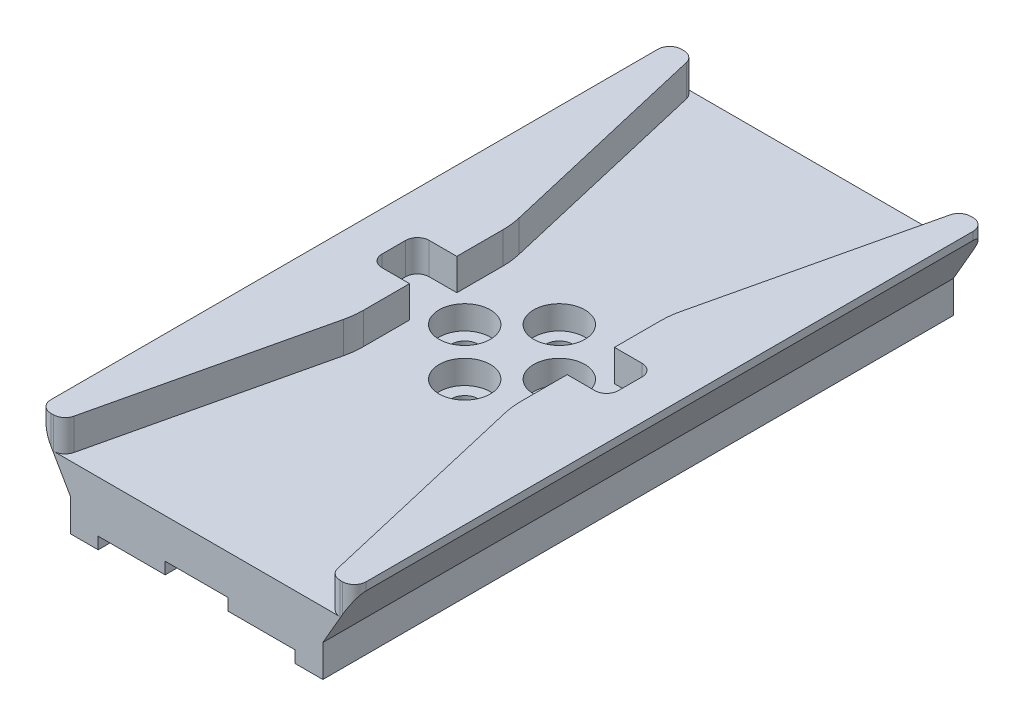
SolidWorks part; units mm, degrees
material "Сплав 2024"
ref_plane "Спереди" through (0, 0, 0) normal (0, 0, 1) x (1, 0, 0)
ref_plane "Сверху" through (0, 0, 0) normal (0, 1, 0) x (1, 0, 0)
ref_plane "Справа" through (0, 0, 0) normal (1, 0, 0) x (0, 0, -1)
sketch "Эскиз1" plane through (0, 0, 0) normal (0, 0, 1) x (1, 0, 0)
  line L0 (-20, 5) -> (-16, -1.9282)
  line L1 (-20, 6) -> (20, 6)
  line L2 (-25.6942, 6) -> (28.5829, 6) construction
  line L3 (-16, -6) -> (16, -6)
  line L4 (0, 6) -> (0, -6) construction
  line L5 (-22.304, 8.9907) -> (-15.6808, -2.4811) construction
  line L7 (-16, -1.9282) -> (-16, -6)
  line L9 (-20, 6) -> (-20, 5)
  line L10 (16, -1.9282) -> (16, -6)
  line L11 (20, 5) -> (16, -1.9282)
  line L12 (20, 6) -> (20, 5)
  point P15 (-20.5774, 6)
  dimension "D1" = 16
  dimension "D2" = 12
  dimension "D3" = 60
  dimension "D4" = 20.5774
  dimension "D6" = 20
  dimension "D7" = 1
extrude "Бобышка-Вытянуть1" add sketch "Эскиз1" along normal blind 80
sketch "Эскиз2" plane through (0, 6, 0) normal (0, 1, 0) x (1, 0, 0)
  line L0 (0, 0) -> (0, -80) construction
  line L1 (20, 0) -> (-20, 0) construction
  line L2 (20, -80) -> (-20, -80) construction
  line L3 (-17, 0) -> (-17, -80) construction
  line L4 (10, -50) -> (17, -80)
  line L5 (-17, 0) -> (-10, -30)
  line L6 (-10, -30) -> (-10, -50)
  line L7 (-10, -50) -> (-17, -80)
  line L8 (10, -30) -> (10, -50)
  line L9 (17, 0) -> (10, -30)
  line L10 (20, -40) -> (-20, -40) construction
  line L11 (-17, 0) -> (17, 0)
  line L12 (17, -80) -> (-17, -80)
  line L20 (-20, -80) -> (-20, 0) construction
  line L21 (20, -80) -> (20, 0) construction
  point P24 (-10, -40)
  dimension "D1" = 10
  dimension "D2" = 3
  dimension "D3" = 20
extrude "Вырез-Вытянуть1" cut sketch "Эскиз2" against normal blind 4
sketch "Эскиз3" plane through (0, 6, 0) normal (0, 1, 0) x (1, 0, 0)
  line L0 (20, -40) -> (-20, -40) construction
  line L4 (-10, -37) -> (-15, -37)
  line L5 (-10, -37) -> (-10, -43)
  line L6 (-10, -43) -> (-15, -43)
  line L7 (-15, -37) -> (-15, -43)
  line L8 (0, 0) -> (0, -80) construction
  line L9 (17, 0) -> (-17, 0) construction
  line L10 (-17, -80) -> (17, -80) construction
  line L11 (10, -37) -> (10, -43)
  line L12 (10, -43) -> (15, -43)
  line L13 (15, -37) -> (15, -43)
  line L14 (10, -37) -> (15, -37)
  line L15 (-10, -30) -> (-10, -50) construction
  line L16 (20, -80) -> (20, 0) construction
  line L17 (-20, -80) -> (-20, 0) construction
  point P12 (-10, -40)
  dimension "D1" = 6
  dimension "D2" = 5
extrude "Вырез-Вытянуть2" cut sketch "Эскиз3" against normal blind 4
fillet "Скругление1" radius 1.5 12 edges at (20, 5.5, 0) (20, 5.5, 80) (-20, 5.5, 80) (-20, 5.5, 0) (-15, 4, 43) (-15, 4, 37) (17, 4, 80) (-17, 4, 80) (17, 4, 0) (-17, 4, 0) (15, 4, 43) (15, 4, 37)
fillet "Скругление2" radius 10 4 edges at (10, 4, 50) (10, 4, 30) (-10, 4, 30) (-10, 4, 50)
sketch "Эскиз4" plane through (0, 2, 0) normal (0, 1, 0) x (1, 0, 0)
  line L0 (0, 0) -> (0, -80) construction
  line L1 (-18.1903, -80) -> (18.1903, -80) construction
  line L2 (20, -40) -> (-20, -40) construction
  line L5 (20, -78.5) -> (20, -1.5) construction
  line L6 (-20, -78.5) -> (-20, -1.5) construction
  circle A0 centre (0, -40) radius 6 construction
  dimension "D1" = 12
hole_wizard "Цековка для винта с внутренним шестигранником M31" positions "Эскиз6" profile "Эскиз5" counterbore size "M3" standard "Ansi Metric" end condition through all
sketch "Эскиз6" plane through (0, 2, 0) normal (0, 1, 0) x (1, 0, 0)
  line L0 (0, 0) -> (0, -80) construction
  line L1 (20, -40) -> (-20, -40) construction
  circle A0 centre (0, -40) radius 6 construction
  point P0 (0, -34)
  point P2 (6, -40)
  point P4 (0, -46)
  point P6 (-6, -40)
sketch "Эскиз5" plane through (0, 2, 34) normal (1, 0, 0) x (0, 0, 1)
  line L0 (0, 0) -> (0, 8)
  line L1 (0, 8) -> (1.7, 8)
  line L3 (1.7, 8) -> (1.7, 3)
  line L4 (1.7, 3) -> (3.25, 3)
  line L5 (3.25, 3) -> (3.25, 0)
  line L7 (3.25, 0) -> (0, 0)
  line L11 (0, -6.35) -> (0, 107.95) construction
  dimension "Диаметр сквозного отверстия" = 3.4
  dimension "Глубина сквозного отверстия" = 8
  dimension "Диаметр цековки" = 6.5
  dimension "Глубина цековки" = 3
sketch "Эскиз7" plane through (0, -6, 0) normal (0, -1, 0) x (1, 0, 0)
  line L0 (0, 80) -> (0, 0) construction
  line L2 (-11.5, 77) -> (11.5, 77)
  line L3 (-11.5, 77) -> (-11.5, 51)
  line L5 (-16, 80) -> (16, 80) construction
  line L6 (11.5, 77) -> (11.5, 51)
  line L7 (-11.5, 77) -> (11.5, 51) construction
  line L8 (-11.5, 51) -> (11.5, 77) construction
  arc A0 (-11.5, 51) -> (11.5, 51) centre (0, 19) cw
  point P0 (0, 64)
  dimension "D2" = 26
  dimension "D5" = 45
  dimension "D1" = 3
  dimension "D3" = 23
  dimension "D4" = 26
extrude "Вырез-Вытянуть3" cut sketch "Эскиз7" against normal blind 7
sketch "Эскиз8" plane through (0, 1, 0) normal (0, -1, 0) x (1, 0, 0)
  line L0 (0, 80) -> (0, 0) construction
  line L1 (-16, 80) -> (16, 80) construction
  line L2 (-16, 61.2) -> (16, 61.2) construction
  line L3 (-16, 80) -> (-16, 0) construction
  line L4 (16, 80) -> (16, 0) construction
  line L6 (13.1, 58.95) -> (7.1, 63.45) construction
  line L7 (-13.1, 63.45) -> (-7.1, 63.45)
  line L8 (-13.1, 63.45) -> (-13.1, 58.95)
  line L9 (-13.1, 58.95) -> (-7.1, 58.95)
  line L10 (13.1, 63.45) -> (7.1, 58.95) construction
  line L11 (-13.1, 63.45) -> (-7.1, 58.95) construction
  line L12 (-13.1, 58.95) -> (-7.1, 63.45) construction
  line L13 (13.1, 58.95) -> (7.1, 58.95)
  line L14 (13.1, 63.45) -> (13.1, 58.95)
  line L15 (13.1, 63.45) -> (7.1, 63.45)
  arc A0 (-7.1, 58.95) -> (-7.1, 63.45) centre (-7.1, 61.2) ccw
  arc A1 (7.1, 58.95) -> (7.1, 63.45) centre (7.1, 61.2) cw
  point P17 (-10.1, 61.2)
  point P24 (10.1, 61.2)
  dimension "D1" = 7.1
  dimension "D2" = 4.5
  dimension "D3" = 10.2
  dimension "D4" = 3
extrude "Бобышка-Вытянуть2" add sketch "Эскиз8" along normal blind 3
hole_wizard "Отверстие обработанное метчиком M3x0.53" positions "Эскиз10" profile "Эскиз9" tap size "M3x0.5" standard "Ansi Metric"
sketch "Эскиз10" plane through (0, -2, 0) normal (0, -1, 0) x (-1, 0, 0)
  point P0 (7.1, -61.2)
  point P2 (-7.1, -61.2)
sketch "Эскиз9" plane through (-7.1, -2, 61.2) normal (1, 0, 0) x (0, 0, -1)
  line L0 (0, 0) -> (0, 3.7511)
  line L1 (0, 3.7511) -> (1.25, 3)
  line L2 (1.25, 3) -> (1.25, 0)
  line L5 (1.25, 0) -> (0, 0)
  line L10 (0, 3.7511) -> (-1.25, 3) construction
  line L11 (0, -6.35) -> (0, 107.95) construction
  dimension "Диаметр сверла" = 2.5
  dimension "Глубина сверла" = 3
  dimension "Угол заточки сверла" = 118
cosmetic thread "Отверстие резьбы7" parameters "D1"=3, "D2"=3
cosmetic thread "Отверстие резьбы8" parameters "D1"=3, "D2"=3
sketch "Эскиз12" plane through (0, 1, 0) normal (0, -1, 0) x (1, 0, 0)
  line L0 (0, 77) -> (0, 51) construction
  line L1 (11.5, 77) -> (-11.5, 77) construction
  line L2 (-11.5, 51) -> (11.5, 51) construction
  line L3 (-1.8247, 64) -> (1.8247, 64) construction
  line L4 (-13.6614, 76) -> (7.1704, 76) construction
  line L5 (-11.5, 80.8402) -> (-11.5, 69.1924) construction
  line L6 (-11.5, 77) -> (-11.5, 51) construction
  circle A0 centre (-11.5, 76) radius 2
  circle A3 centre (11.5, 76) radius 2
  circle A4 centre (11.5, 52) radius 2
  circle A6 centre (-11.5, 52) radius 2
  point P14 (0, 64)
  dimension "D3" = 4
  dimension "D2" = 1
sketch "Эскиз15" plane through (0, 1, 0) normal (0, -1, 0) x (1, 0, 0)
  line L0 (0, 77) -> (0, 51) construction
  line L1 (11.5, 77) -> (-11.5, 77) construction
  line L2 (-13.8501, 64) -> (13.8501, 64) construction
  line L4 (-11.5, 51) -> (11.5, 51) construction
  line L5 (11.5, 51) -> (11.5, 77) construction
  line L7 (11.5, 77) -> (-11.5, 77) construction
  line L8 (-11.5, 77) -> (-11.5, 63.45) construction
  line L9 (-11.5, 77) -> (-11.5, 51) construction
  circle A0 centre (-11.5, 51) radius 2.5
  circle A1 centre (11.5, 51) radius 2.5
  circle A2 centre (-9, 77) radius 2.5
  circle A3 centre (9, 77) radius 2.5
  point P8 (0, 64)
  dimension "D1" = 5
  dimension "D2" = 5
  dimension "D3" = 5
extrude "Бобышка-Вытянуть5" add sketch "Эскиз15" along normal up to surface (7 mm away) up to face at (0, -6, 64.5009)
fillet "Скругление8" radius 3 12 edges at (11.5, -2.5, 53.5) (9.1178, -2.5, 51.7584) (-9.1178, -2.5, 51.7584) (-11.5, -2.5, 53.5) (-11.5, -0.5, 58.95) (11.5, -0.5, 58.95) (11.5, -0.5, 63.45) (-11.5, -0.5, 63.45) (-11.5, -2.5, 77) (11.5, -2.5, 77) (6.5, -2.5, 77) (-6.5, -2.5, 77)
sketch "Эскиз16" plane through (0, -6, 0) normal (0, -1, 0) x (1, 0, 0)
  line L0 (-16, 80) -> (16, 80) construction
  line L1 (-12.5, 80) -> (12.5, 80)
  line L70 (-12.5, 54.3541) -> (-12.5, 80)
  line L71 (12.5, 54.3541) -> (12.5, 80)
  line L72 (-11.5, 71.5228) -> (-11.5, 55.6098) construction
  line L73 (11.5, 55.6098) -> (11.5, 71.5228) construction
  arc A0 (7.2531, 52.2211) -> (-7.2531, 52.2211) centre (0, 19) ccw construction
  arc A1 (7.2531, 52.2211) -> (-7.2531, 52.2211) centre (0, 19) ccw construction
  arc A2 (8.0001, 51.0194) -> (-8.0001, 51.0194) centre (0, 19) ccw
  arc A3 (7.0398, 51.2441) -> (-7.0398, 51.2441) centre (0, 19) ccw construction
  arc A42 (-12.5, 54.3541) -> (-8.0001, 51.0194) centre (-11.5, 51) ccw
  arc A43 (8.0001, 51.0194) -> (12.5, 54.3541) centre (11.5, 51) ccw
  dimension "D3" = 7
  dimension "D4" = 7
  dimension "D6" = 1
  dimension "D7" = 1
  dimension "D2" = 1
extrude "Вырез-Вытянуть6" cut sketch "Эскиз16" against normal blind 1.5
fillet "Скругление9" radius 3 4 edges at (12.5, -5.25, 54.3541) (8.0001, -5.25, 51.0194) (-8.0001, -5.25, 51.0194) (-12.5, -5.25, 54.3541)
hole_wizard "Отверстие обработанное метчиком M3x0.52" positions "Эскиз19" profile "Эскиз18" tap size "M3x0.5" standard "Ansi Metric"
sketch "Эскиз19" plane through (0, -4.5, 0) normal (0, -1, 0) x (-1, 0, 0)
  point P0 (11.5, -51)
  point P3 (-11.5, -51)
  point P6 (-9, -77)
  point P9 (9, -77)
sketch "Эскиз18" plane through (-11.5, -4.5, 51) normal (1, 0, 0) x (0, 0, -1)
  line L0 (0, 0) -> (0, 6.2501)
  line L1 (0, 6.2501) -> (1.25, 5.499)
  line L2 (1.25, 5.499) -> (1.25, 0)
  line L5 (1.25, 0) -> (0, 0)
  line L10 (0, 6.2501) -> (-1.25, 5.499) construction
  line L11 (0, -6.35) -> (0, 107.95) construction
  dimension "Диаметр сверла" = 2.5
  dimension "Глубина сверла" = 5.499
  dimension "Угол заточки сверла" = 118
cosmetic thread "Отверстие резьбы9" parameters "D1"=5.5, "D2"=3
cosmetic thread "Отверстие резьбы10" parameters "D1"=5.5, "D2"=3
cosmetic thread "Отверстие резьбы11" parameters "D1"=5.5, "D2"=3
cosmetic thread "Отверстие резьбы12" parameters "D1"=5.5, "D2"=3
sketch "Эскиз20" plane through (0, -4.5, 0) normal (0, -1, 0) x (1, 0, 0)
  line L0 (0, 80) -> (0, 67.2176) construction
  line L1 (12.5, 80) -> (-12.5, 80) construction
  line L2 (-4.3902, 77) -> (4.3902, 77) construction
  line L3 (-4, 80) -> (4, 80)
  line L4 (-4, 80) -> (-4, 77)
  line L5 (-4, 77) -> (4, 77)
  line L6 (4, 80) -> (4, 77)
  line L7 (-4, 80) -> (4, 77) construction
  line L8 (-4, 77) -> (4, 80) construction
  point P5 (0, 78.5)
  dimension "D1" = 8
extrude "Вырез-Вытянуть7" cut sketch "Эскиз20" against normal blind 1.5
sketch "Эскиз21" plane through (0, -2, 0) normal (0, -1, 0) x (1, 0, 0)
  line L0 (11.5, 61.2) -> (-11.5, 61.2) construction
  line L1 (11.5, 55.95) -> (11.5, 66.45) construction
  line L2 (-11.5, 55.95) -> (-11.5, 66.45) construction
  line L3 (0, 53.0037) -> (0, 77) construction
  line L4 (4.3902, 77) -> (-4.3902, 77) construction
  line L6 (-5.5, 63.7) -> (5.5, 63.7)
  line L7 (-5.5, 63.7) -> (-5.5, 58.7)
  line L8 (-5.5, 58.7) -> (5.5, 58.7)
  line L9 (5.5, 63.7) -> (5.5, 58.7)
  line L10 (-5.5, 63.7) -> (5.5, 58.7) construction
  line L11 (-5.5, 58.7) -> (5.5, 63.7) construction
  arc A0 (7.2531, 52.2211) -> (-7.2531, 52.2211) centre (0, 19) ccw construction
  point P13 (0, 61.2)
  dimension "D1" = 11
  dimension "D2" = 5
extrude "Вырез-Вытянуть8" cut sketch "Эскиз21" against normal up to surface (3 mm away) up to face at (0, 1, 62.8736)
